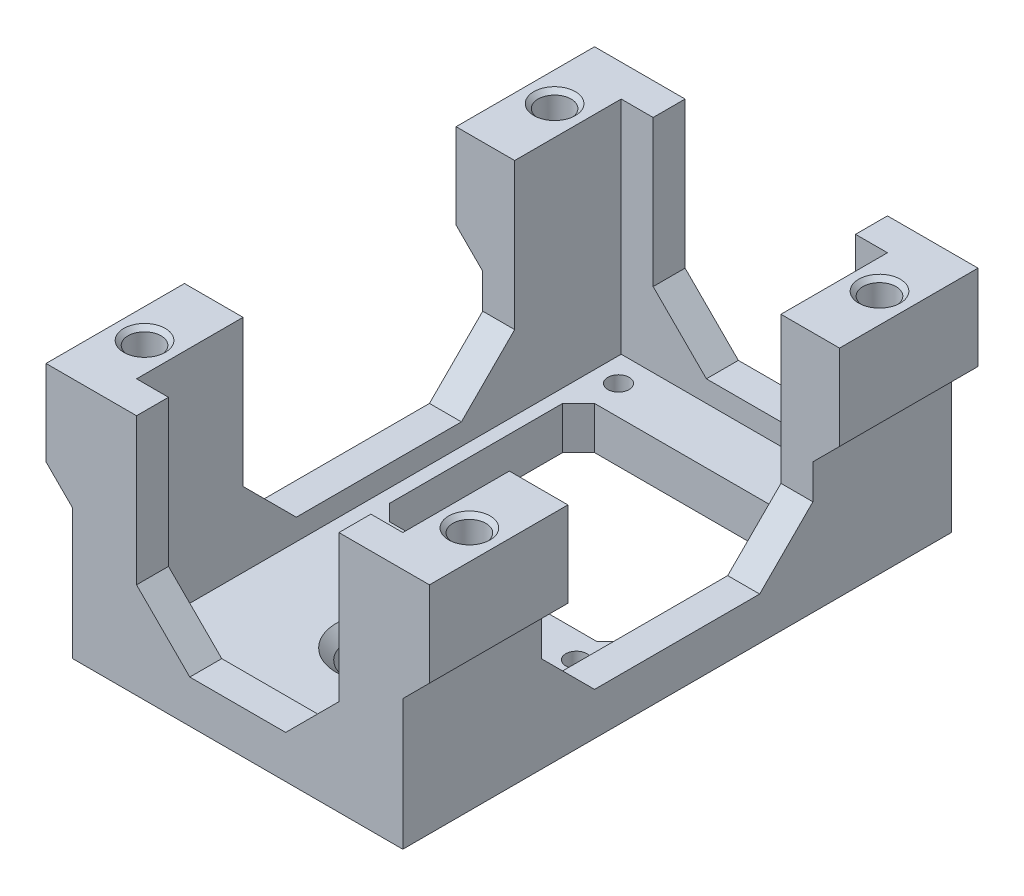
SolidWorks part; units mm, degrees
ref_plane "Front Plane" through (0, 0, 0) normal (0, 0, 1) x (1, 0, 0)
ref_plane "Top Plane" through (0, 0, 0) normal (0, 1, 0) x (1, 0, 0)
ref_plane "Right Plane" through (0, 0, 0) normal (1, 0, 0) x (0, 0, -1)
sketch "Sketch1" plane through (0, 0, 0) normal (0, 1, 0) x (1, 0, 0)
  line L1 (-12.5, -22.75) -> (12.5, -22.75)
  line L2 (-12.5, -22.75) -> (-12.5, 22.75)
  line L3 (-12.5, 22.75) -> (12.5, 22.75)
  line L4 (12.5, -22.75) -> (12.5, 22.75)
  line L5 (-12.5, -22.75) -> (12.5, 22.75) construction
  line L6 (-12.5, 22.75) -> (12.5, -22.75) construction
  point P0 (0, 0)
  dimension "D1" = 25
  dimension "D2" = 45.5
extrude "Boss-Extrude1" add sketch "Sketch1" along normal blind 4
sketch "Sketch2" plane through (0, 4, 0) normal (0, 1, 0) x (1, 0, 0)
  line L0 (12.5, 22.75) -> (-12.5, 22.75) construction
  line L1 (-10.25, -4.2) -> (10.25, -4.2) construction
  line L2 (-10.25, -4.2) -> (-10.25, 20.25) construction
  line L3 (-10.25, 20.25) -> (10.25, 20.25) construction
  line L4 (10.25, -4.2) -> (10.25, 20.25) construction
  line L5 (-10.25, -4.2) -> (10.25, 20.25) construction
  line L6 (-10.25, 20.25) -> (10.25, -4.2) construction
  circle A0 centre (-10.25, 20.25) radius 1
  circle A1 centre (10.25, 20.25) radius 1
  circle A2 centre (10.25, -4.2) radius 1
  circle A3 centre (-10.25, -4.2) radius 1
  point P0 (0, 8.025)
  dimension "D4" = 2
  dimension "D1" = 20.5
  dimension "D2" = 24.45
  dimension "D3" = 2.5
extrude "Cut-Extrude1" cut sketch "Sketch2" against normal through all
sketch "Sketch3" plane through (0, 4, 0) normal (0, 1, 0) x (1, 0, 0)
  line L1 (-11.25, -1.75) -> (11.25, -1.75)
  line L2 (-11.25, -1.75) -> (-11.25, 17.5)
  line L3 (-11.25, 17.5) -> (11.25, 17.5)
  line L4 (11.25, -1.75) -> (11.25, 17.5)
  line L5 (-11.25, -1.75) -> (11.25, 17.5) construction
  line L6 (-11.25, 17.5) -> (11.25, -1.75) construction
  circle A0 centre (-10.25, 20.25) radius 1 construction
  point P0 (0, 7.875)
  dimension "D2" = 2.75
  dimension "D1" = 22.5
  dimension "D3" = 19.25
extrude "Cut-Extrude2" cut sketch "Sketch3" against normal up to vertex (4 mm away) up to point (0, 0, 0)
chamfer "Chamfer1" distance 1.5 angle 45 4 edges at (11.25, 2, 1.75) (11.25, 2, -17.5) (-11.25, 2, 1.75) (-11.25, 2, -17.5)
sketch "Sketch4" plane through (0, 4, 0) normal (0, 1, 0) x (1, 0, 0)
  line L0 (-9.75, -1.75) -> (9.75, -1.75) construction
  circle A0 centre (0, -12.5) radius 3
  dimension "D1" = 6
  dimension "D2" = 10.75
extrude "Cut-Extrude3" cut sketch "Sketch4" against normal through all
sketch "Sketch11" plane through (0, 0, 0) normal (0, -1, 0) x (1, 0, 0)
  line L0 (12.5, -22.75) -> (-12.5, -22.75) construction
  line L1 (-12.5, -22.75) -> (-12.5, 22.75) construction
  line L2 (-12.5, 22.75) -> (12.5, 22.75) construction
  line L3 (12.5, 22.75) -> (12.5, -22.75) construction
  line L4 (12.5, -22.75) -> (-12.5, -22.75)
  line L5 (-12.5, -22.75) -> (-12.5, 22.75)
  line L6 (-12.5, 22.75) -> (12.5, 22.75)
  line L7 (12.5, 22.75) -> (12.5, -22.75)
  line L8 (-15.5, -25.75) -> (-15.5, 25.75)
  line L9 (-15.5, 25.75) -> (15.5, 25.75)
  line L10 (15.5, 25.75) -> (15.5, -25.75)
  line L11 (15.5, -25.75) -> (-15.5, -25.75)
  dimension "D1" = 3
extrude "Boss-Extrude5" add sketch "Sketch11" against normal blind 6
sketch "Sketch12" plane through (0, 6, 0) normal (0, 1, 0) x (1, 0, 0)
  line L0 (-15.5, 25.75) -> (-9.5, 25.75)
  line L1 (-15.5, 25.75) -> (15.5, 25.75) construction
  line L2 (-9.5, 25.75) -> (-9.5, 22.75)
  line L3 (12.5, 22.75) -> (-12.5, 22.75) construction
  line L4 (-9.5, 22.75) -> (-12.5, 22.75)
  line L5 (-12.5, 22.75) -> (12.5, 22.75) construction
  line L6 (-12.5, 22.75) -> (-12.5, 12.75)
  line L7 (-12.5, 22.75) -> (-12.5, -22.75) construction
  line L8 (-12.5, 12.75) -> (-15.5, 12.75)
  line L9 (-15.5, -25.75) -> (-15.5, 25.75) construction
  line L10 (-15.5, 12.75) -> (-15.5, 25.75)
  dimension "D1" = 3
  dimension "D2" = 10
extrude "Boss-Extrude6" add sketch "Sketch12" along normal blind 18.75
sketch "Sketch14" plane through (0, 24.75, 0) normal (0, 1, 0) x (1, 0, 0)
  line L0 (-9.5, 25.75) -> (-15.5, 25.75) construction
  line L1 (-12.5, 12.75) -> (-18, 12.75)
  line L2 (-12.5, 12.75) -> (-12.5, 25.75)
  line L3 (-12.5, 25.75) -> (-18, 25.75)
  line L4 (-18, 12.75) -> (-18, 25.75)
  dimension "D1" = 5.5
extrude "Boss-Extrude7" add sketch "Sketch14" against normal blind 8
sketch "Sketch15" plane through (0, 24.75, 0) normal (0, 1, 0) x (1, 0, 0)
  line L0 (-18, 12.75) -> (-12.5, 12.75) construction
  line L1 (-18, 25.75) -> (-18, 12.75) construction
  circle A0 centre (-15.25, 19.25) radius 1.55
  point P2 (-15.25, 12.75)
  point P3 (-18, 19.25)
  dimension "D1" = 3.1
extrude "Cut-Extrude5" cut sketch "Sketch15" against normal blind 3
mirror "Mirror2" about plane through (0, 0, 0) normal (1, 0, 0) of "Cut-Extrude5", "Boss-Extrude7", "Boss-Extrude6" second plane through (0, 0, 0) second plane normal (0, 0, 1)
chamfer "Chamfer3" distance 2.5 angle 45 12 edges at (-15.5, 16.75, -19.25) (-16.75, 16.75, -12.75) (-16.75, 16.75, -25.75) (-15.5, 16.75, 19.25) (-16.75, 16.75, 25.75) (-16.75, 16.75, 12.75) (15.5, 16.75, -19.25) (16.75, 16.75, -25.75) (16.75, 16.75, -12.75) (15.5, 16.75, 19.25) (16.75, 16.75, 12.75) (16.75, 16.75, 25.75)
chamfer "Chamfer4" distance 5 angle 45 8 edges at (-14, 6, -12.75) (-9.5, 6, -24.25) (-14, 6, 12.75) (-9.5, 6, 24.25) (14, 6, -12.75) (9.5, 6, -24.25) (14, 6, 12.75) (9.5, 6, 24.25)
chamfer "Chamfer5" distance 2 angle 45 4 edges at (0, 0, 25.75) (15.5, 0, 0) (0, 0, -25.75) (-15.5, 0, 0)
sketch "Sketch16" plane through (0, 0, 0) normal (0, -1, 0) x (1, 0, 0)
  circle A0 centre (-10.25, 4.2) radius 2
  circle A1 centre (10.25, 4.2) radius 2
  circle A2 centre (10.25, -20.25) radius 2
  circle A3 centre (-10.25, -20.25) radius 2
  dimension "D1" = 4
extrude "Cut-Extrude6" cut sketch "Sketch16" against normal blind 1.5
chamfer "Chamfer6" distance 1 angle 45 2 edges at (0, 4, 15.5) (0, 0, 15.5)
chamfer "Chamfer7" distance 0.4 angle 45 4 edges at (-15.25, 24.75, -17.7) (-15.25, 24.75, 17.7) (15.25, 24.75, -17.7) (15.25, 24.75, 17.7)
sketch "Sketch17" plane through (0, 21.75, 0) normal (0, 1, 0) x (1, 0, 0)
  circle A0 centre (-15.25, 19.25) radius 1
  circle A1 centre (15.25, 19.25) radius 1
  circle A2 centre (15.25, -19.25) radius 1
  circle A3 centre (-15.25, -19.25) radius 1
  dimension "D1" = 2
extrude "Cut-Extrude7" cut sketch "Sketch17" against normal blind 4
